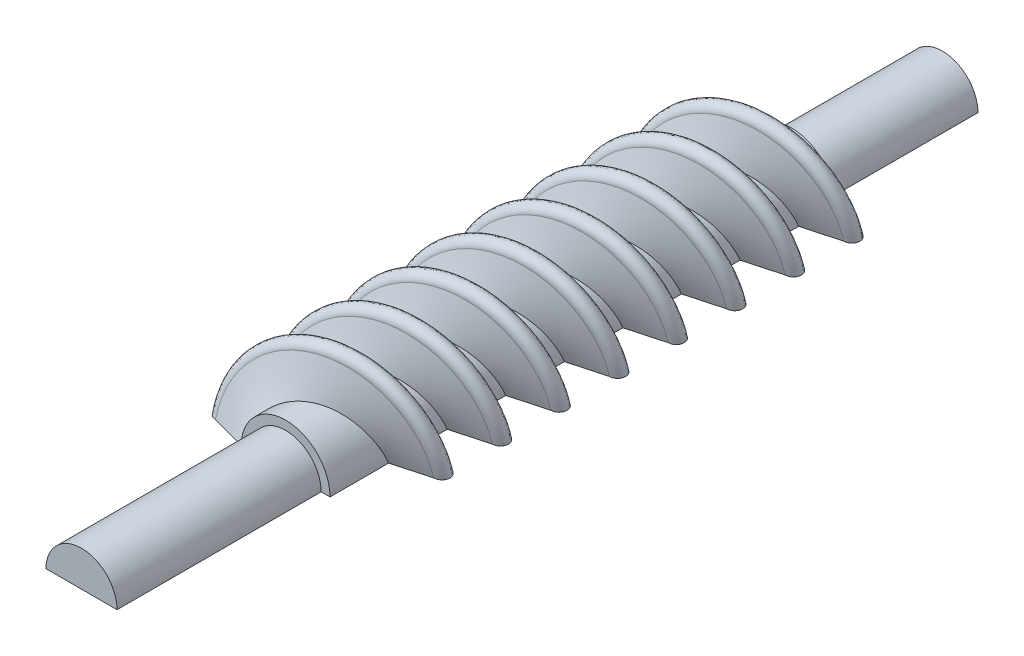
SolidWorks part; units mm, degrees
ref_plane "Plan de face" through (0, 0, 0) normal (0, 0, 1) x (1, 0, 0)
ref_plane "Plan de dessus" through (0, 0, 0) normal (0, 1, 0) x (1, 0, 0)
ref_plane "Plan de droite" through (0, 0, 0) normal (1, 0, 0) x (0, 0, -1)
sketch "Esquisse1" plane through (0, 0, 0) normal (0, 0, 1) x (1, 0, 0)
  circle A0 centre (0, 0) radius 5
  dimension "D1" = 10
extrude "Boss.-Extru.1" add sketch "Esquisse1" along normal blind 55
sketch "Esquisse3" plane through (0, 0, 55) normal (0, 0, 1) x (1, 0, 0)
  circle A0 centre (0, 0) radius 5
curve "Hélice/Spirale1" pitch 13.2 height 52.8 radius 5 centre (0, 0, 55) axis (0, 0, -1) start towards (-1, 0, 0)
sketch "Esquisse4" plane through (0, 0, 0) normal (0, 1, 0) x (1, 0, 0)
  line L0 (-5, -55) -> (-9, -55) construction
  line L1 (-5, 0) -> (-5, -55) construction
  line L2 (-9, -54.1) -> (-5, -53)
  line L3 (-9, -55.9) -> (-5, -57)
  line L5 (-5, -53) -> (-4.702, -53)
  line L6 (-4.702, -53) -> (-4.702, -57)
  line L7 (-4.702, -57) -> (-5, -57)
  arc A1 (-9, -54.1) -> (-9, -55.9) centre (-9, -55) ccw
  spline S0 degree 3 poles (-5, -55) (-5, -54.7265) (-4.7397, -54.1743) (-3.6276, -53.3502) (-1.9632, -52.525) (0, -51.7) (1.9632, -50.875) (3.6276, -50.05) (4.7397, -49.225) (5.1302, -48.4) (4.7397, -47.575) (3.6276, -46.75) (1.4084, -45.65) (-1.4084, -44.55) (-3.6276, -43.45) (-4.7397, -42.625) (-5.1302, -41.8) (-4.7397, -40.975) (-3.6276, -40.15) (-1.4084, -39.05) (1.4084, -37.95) (3.6276, -36.85) (4.7397, -36.025) (5.1302, -35.2) (4.7397, -34.375) (3.6276, -33.55) (1.4084, -32.45) (-1.4084, -31.35) (-3.6276, -30.25) (-4.7397, -29.425) (-5.1302, -28.6) (-4.7397, -27.775) (-3.6276, -26.95) (-1.4084, -25.85) (1.4084, -24.75) (3.6276, -23.65) (4.7397, -22.825) (5.1302, -22) (4.7397, -21.175) (3.6276, -20.35) (1.4084, -19.25) (-1.4084, -18.15) (-3.6276, -17.05) (-4.7397, -16.225) (-5.1302, -15.4) (-4.7397, -14.575) (-3.6276, -13.75) (-1.4084, -12.65) (1.4084, -11.55) (3.6276, -10.45) (4.7397, -9.625) (5.1302, -8.8) (4.7397, -7.975) (3.6276, -7.15) (1.9632, -6.325) (0, -5.5) (-1.9632, -4.675) (-3.6276, -3.8498) (-4.7397, -3.0257) (-5, -2.4735) (-5, -2.2) knots 0 0 0 0 0.015625 0.03125 0.046875 0.0625 0.078125 0.09375 0.109375 0.125 0.140625 0.15625 0.171875 0.203125 0.21875 0.234375 0.25 0.265625 0.28125 0.296875 0.328125 0.34375 0.359375 0.375 0.390625 0.40625 0.421875 0.453125 0.46875 0.484375 0.5 0.515625 0.53125 0.546875 0.578125 0.59375 0.609375 0.625 0.640625 0.65625 0.671875 0.703125 0.71875 0.734375 0.75 0.765625 0.78125 0.796875 0.828125 0.84375 0.859375 0.875 0.890625 0.90625 0.921875 0.9375 0.953125 0.96875 0.984375 1 1 1 1 construction
  dimension "D3" = 0.9
  dimension "D1" = 4
  dimension "D2" = 4
sweep "Balayage2" add profiles "Esquisse4" path "Hélice/Spirale1"
pattern_circular "CirPattern1" count 2 over 360 about axis through (0, 0, 55) along (0, 0, -1) of "Balayage2"
sketch "arbre" plane through (0, 0, 0) normal (0, 0, -1) x (-1, 0, 0)
  circle A0 centre (0, 0) radius 4
  dimension "D1" = 8
extrude "Motor-side" add sketch "arbre" along normal blind 17 separate body
sketch "Sketch1" plane through (0, 0, 55) normal (0, 0, 1) x (1, 0, 0)
  circle A0 centre (0, 0) radius 4
  dimension "D1" = 8
extrude "Bearing-side" add sketch "Sketch1" along normal blind 25
sketch "Sketch2" plane through (0, 0, 55) normal (0, 0, 1) x (1, 0, 0)
  circle A0 centre (0, 0) radius 5
  dimension "D1" = 10
extrude "Boss-Extrude2" add sketch "Sketch2" along normal blind 2
sketch "Sketch3" plane through (0, 0, 80) normal (0, 0, 1) x (1, 0, 0)
  line L9 (-17.0031, 0) -> (18.8779, 0)
  line L10 (-17.0031, 0) -> (-17.0031, -11.3331)
  line L11 (-17.0031, -11.3331) -> (18.8779, -11.3331)
  line L12 (18.8779, 0) -> (18.8779, -11.3331)
extrude "Cut-Extrude1" cut sketch "Sketch3" against normal through all
